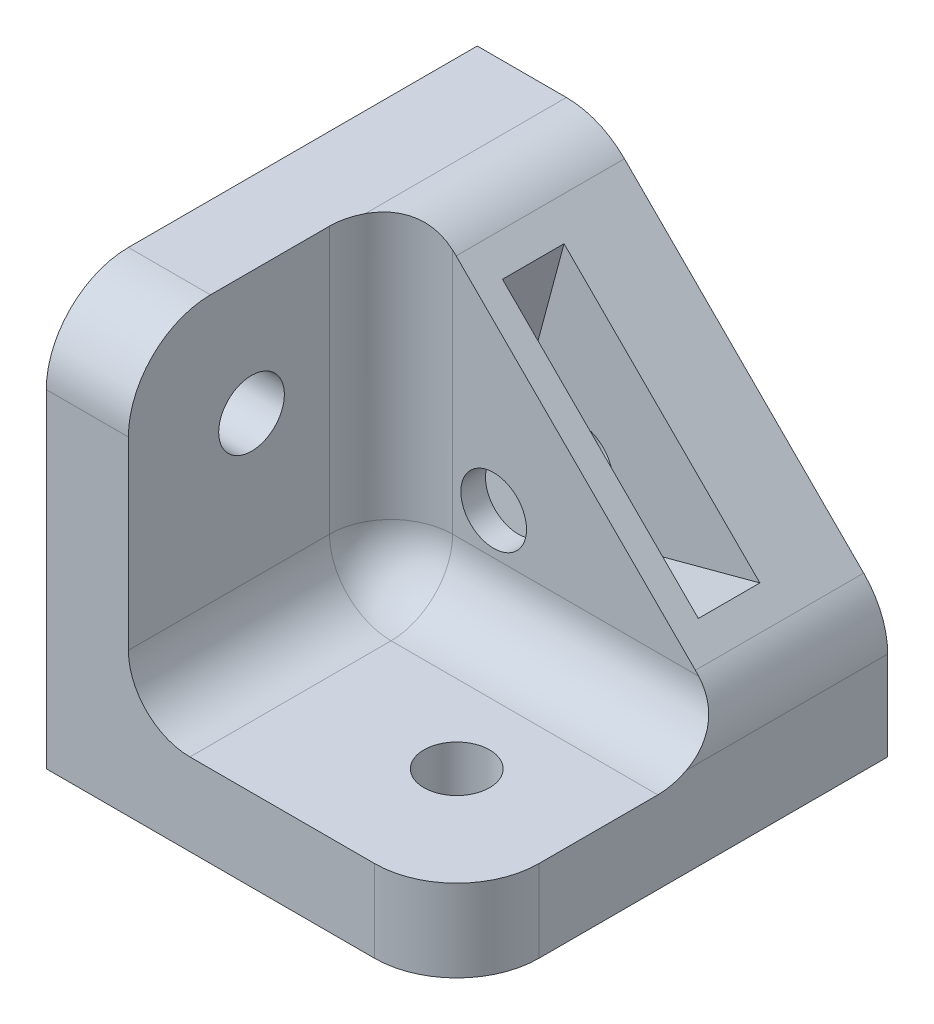
SolidWorks part; units mm, degrees
ref_plane "Front Plane" through (0, 0, 0) normal (0, 0, 1) x (1, 0, 0)
ref_plane "Top Plane" through (0, 0, 0) normal (0, 1, 0) x (1, 0, 0)
ref_plane "Right Plane" through (0, 0, 0) normal (1, 0, 0) x (0, 0, -1)
sketch "Sketch4" plane through (0, 0, 0) normal (0, 0, 1) x (1, 0, 0)
  line L2 (0, 0) -> (0, 20)
  line L3 (0, 20) -> (4, 20)
  line L4 (4, 4) -> (4, 20)
  line L5 (0, 0) -> (20, 0)
  line L7 (4, 4) -> (20, 4)
  line L8 (20, 0) -> (20, 4)
  line L9 (4, 20) -> (6, 20)
  line L10 (6, 20) -> (20, 6)
  line L11 (20, 6) -> (20, 4)
  dimension "D1" = 4
  dimension "D2" = 4
  dimension "D3" = 20
  dimension "D4" = 20
  dimension "D5" = 2
  dimension "D6" = 2
extrude "Boss-Extrude4" add sketch "Sketch4" along normal blind 8.2 separate body contours L5 L8 L7 L4 L3 L2 | L4 L7 region at (0.2828, 10, 0) region at (9.9325, 9.9325, 0)
extrude "Boss-Extrude5" add sketch "Sketch4<4>" along normal blind 21 contours L5 L8 L7 L4 L3 L2 region at (0.2828, 10, 0)
sketch "Sketch4<4>" plane through (0, 0, 0) normal (0, 0, 1) x (1, 0, 0) same geometry as "Sketch4"
hole_wizard "Ø3.2 (3.2) Diameter Hole1" positions "3DSketch2" profile "Sketch6" hole size "Ø3.2" standard "ANSI Metric" end condition through all
sketch3d "3DSketch2"
  line L0 (0, 0, 21) -> (0, 0, 0) construction
  line L1 (0, 0, 0) -> (20, 0, 0) construction
  line L2 (0, 0, 0) -> (0, 20, 0) construction
  point P0 (14, 0, 15)
  point P2 (0, 14, 15)
  point P4 (9, 9, 0)
  dimension "D1" = 14
  dimension "D2" = 14
  dimension "D3" = 15
  dimension "D4" = 15
  dimension "D5" = 9
  dimension "D6" = 9
sketch "Sketch6" plane through (14, 0, 15) normal (1, 0, 0) x (0, 0, -1)
  line L0 (0, 0) -> (0, 20)
  line L1 (0, 20) -> (1.6, 20)
  line L2 (1.6, 20) -> (1.6, 0)
  line L5 (1.6, 0) -> (0, 0)
  line L11 (0, -6.35) -> (0, 107.95) construction
  dimension "Thru Hole Dia." = 3.2
  dimension "Thru Hole Depth" = 20
fillet "Fillet1" radius 3 3 edges at (12, 4, 8.2) (4, 4, 14.6) (4, 12, 8.2)
fillet "Fillet2" radius 4 4 edges at (6, 20, 4.1858) (20, 6, 4.1858) (20, 2, 21) (2, 20, 21)
sketch "Sketch7" plane through (0, 0, 0) normal (0, 0, -1) x (-1, 0, 0)
  line L0 (-8.2284, 17.7716) -> (-5.6412, 8.1161)
  line L1 (-7.1716, 18.8284) -> (-18.8284, 7.1716) construction
  line L2 (-5.6412, 8.1161) -> (-8.1161, 5.6412)
  line L3 (-8.1161, 5.6412) -> (-17.7716, 8.2284)
  line L4 (-13, 13) -> (-6.8787, 6.8787) construction
  line L5 (-8.2284, 17.7716) -> (-17.7716, 8.2284)
  circle A0 centre (-9, 9) radius 1.6 construction
  dimension "D1" = 60
  dimension "D2" = 3.5
  dimension "D3" = 3
extrude "Cut-Extrude2" cut sketch "Sketch7" against normal blind 3 from offset 4 offset against normal yes
equation "\"D2@Sketch4\"=\"D1@Sketch4\""
equation "\"D4@Sketch4\"=\"D3@Sketch4\""
equation "\"D6@Sketch4\"=\"D5@Sketch4\""
